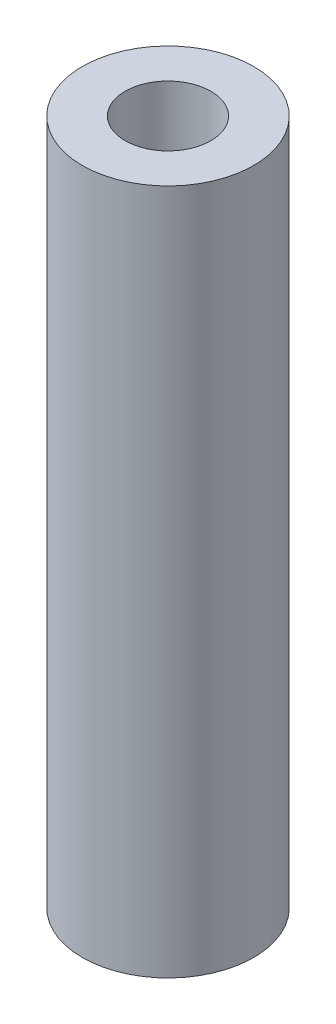
SolidWorks part; units mm, degrees
ref_plane "Front Plane" through (0, 0, 0) normal (0, 0, 1) x (1, 0, 0)
ref_plane "Top Plane" through (0, 0, 0) normal (0, 1, 0) x (1, 0, 0)
ref_plane "Right Plane" through (0, 0, 0) normal (1, 0, 0) x (0, 0, -1)
sketch "Sketch1" plane through (0, 0, 0) normal (0, 1, 0) x (1, 0, 0)
  circle A0 centre (0, 0) radius 38.1
  circle A1 centre (0, 0) radius 19.05
  dimension "D1" = 76.2
  dimension "D2" = 38.1
extrude "Boss-Extrude1" add sketch "Sketch1" along normal blind 304.8
